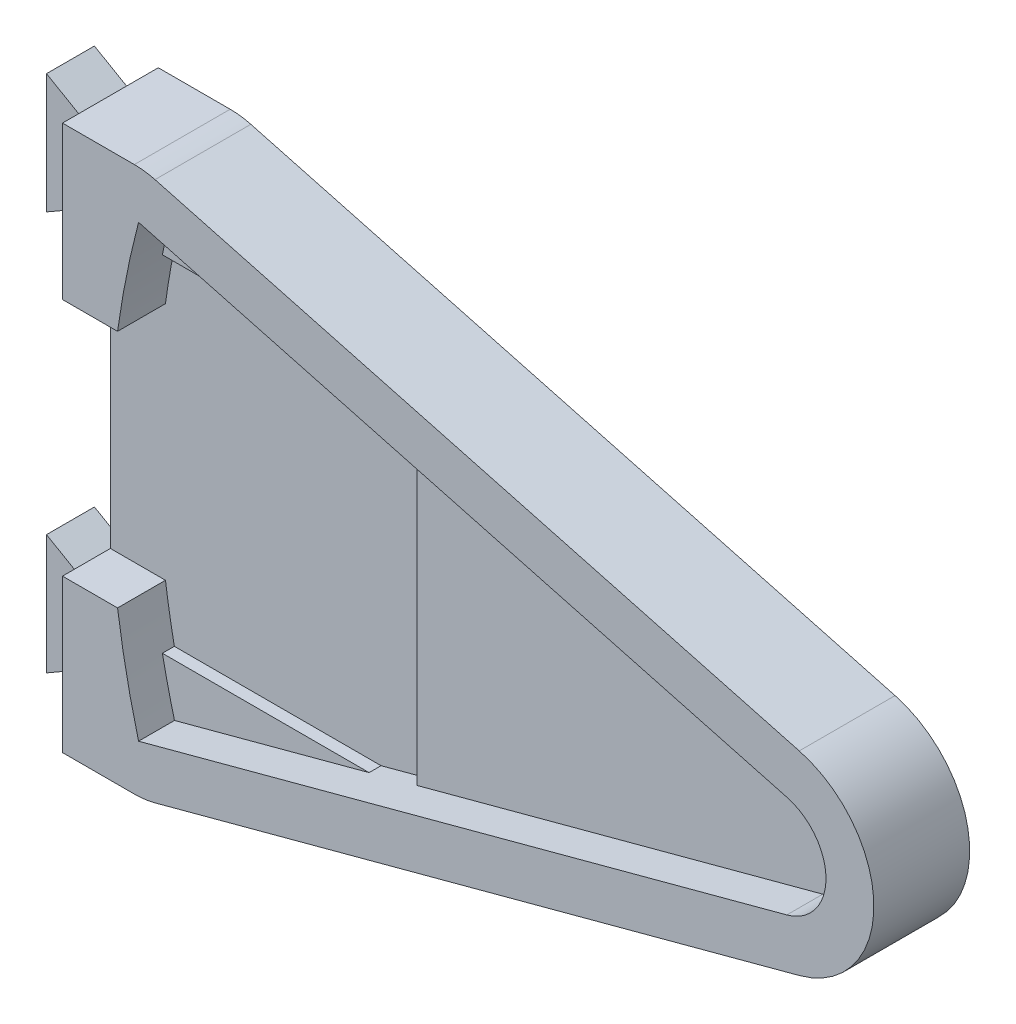
SolidWorks part; units mm, degrees
ref_plane "Front Plane" through (0, 0, 0) normal (0, 0, 1) x (1, 0, 0)
ref_plane "Top Plane" through (0, 0, 0) normal (0, 1, 0) x (1, 0, 0)
ref_plane "Right Plane" through (0, 0, 0) normal (1, 0, 0) x (0, 0, -1)
sketch "Sketch1" plane through (0, 0, 0) normal (0, 0, 1) x (1, 0, 0)
  line L0 (-4.8058, 6.263) -> (-85.8802, 27.9868) construction
  line L1 (-85.8802, -27.9868) -> (-4.8058, -6.263) construction
  line L2 (-89.5, 0) -> (0, 0) construction
  line L3 (-85.9704, -28.1425) -> (-4.7729, -6.3857)
  line L4 (-4.7729, 6.3857) -> (-85.9704, 28.1425)
  line L5 (-83.9089, -33.8018) -> (-3.22, -12.1813)
  line L6 (-3.22, 12.1813) -> (-83.9089, 33.8018)
  line L7 (-95.5, 34.1425) -> (-95.5, -34.1425)
  line L8 (-89.5, 0) -> (-95.5, 0) construction
  line L9 (-84.4175, -33.9381) -> (-3.22, -12.1813) construction
  line L10 (-3.22, 12.1813) -> (-84.4175, 33.9381) construction
  line L11 (-95.5, 34.1425) -> (-86.4971, 34.1425)
  line L12 (-95.5, -34.1425) -> (-86.4971, -34.1425)
  arc A0 (-85.8802, 27.9868) -> (-85.8802, -27.9868) centre (20.5, 0) ccw construction
  arc A1 (-4.8058, -6.263) -> (-4.8058, 6.263) centre (-6.484, 0) ccw construction
  arc A2 (-85.9704, 28.1425) -> (-85.9704, -28.1425) centre (20.5, 0) ccw
  arc A3 (-4.7729, -6.3857) -> (-4.7729, 6.3857) centre (-6.484, 0) ccw
  arc A4 (-3.22, -12.1813) -> (-3.22, 12.1813) centre (-6.484, 0) ccw
  arc A5 (-86.4971, 34.1425) -> (-83.9089, 33.8018) centre (-86.4971, 24.1425) cw
  arc A6 (-86.4971, -34.1425) -> (-83.9089, -33.8018) centre (-86.4971, -24.1425) ccw
  point P6 (0, 0)
  point P23 (-95.5, 0)
  dimension "D1" = 110
  dimension "D2" = 6.484
  dimension "D12" = 10
  dimension "D14" = 10
  dimension "D3" = 81.0744
  dimension "D4" = 81.0744
  dimension "D5" = 21.7238
  dimension "D6" = 21.7238
  dimension "D7" = 55.9737
  dimension "D10" = 6
  dimension "D11" = 6
  dimension "D13" = 6
  dimension "D8" = 0.127
  dimension "D9" = 6
extrude "Boss-Extrude1" add sketch "Sketch1" along normal blind 6 contours L3 A3 L4 A2 | L12 A6 L5 A4 L6 A5 L11 L7 A3 L3 A2 L4 region at (-54.6517, 0, 0) region at (-85.3516, -32.8431, 0)
extrude "Boss-Extrude2" add sketch "Sketch1<3>" along normal blind 6 from surface starting at face at (-66.1103, 0, 6)
sketch "Sketch1<3>" plane through (0, 0, 0) normal (0, 0, 1) x (1, 0, 0) same geometry as "Sketch1"
sketch "Sketch2" plane through (0, 0, 0) normal (0, 0, 1) x (1, 0, 0)
  line L4 (0, 0) -> (-95.5, 0) construction
  line L6 (-95.5, -34.1425) -> (-95.5, 34.1425) construction
  line L7 (-95.5, 27.8812) -> (-103.5, 32.5)
  line L8 (-103.5, 32.5) -> (-103.5, 17.5)
  line L9 (-103.5, 17.5) -> (-95.5, 22.1188)
  line L10 (-103.5, -17.5) -> (-95.5, -22.1188)
  line L11 (-103.5, -32.5) -> (-103.5, -17.5)
  line L12 (-95.5, -27.8812) -> (-103.5, -32.5)
  line L13 (-95.5, 27.8812) -> (-95.5, 22.1188)
  line L14 (-95.5, -22.1188) -> (-95.5, -27.8812)
  point P4 (-103.5, 25)
  dimension "D1" = 25
  dimension "D2" = 60
  dimension "D3" = 60
  dimension "D4" = 15
  dimension "D5" = 8
extrude "Boss-Extrude3" add sketch "Sketch2" along normal blind 6
sketch "Sketch3" plane through (-95.5, 0, 0) normal (-1, 0, 0) x (0, 0, 1)
  line L0 (12, -34.1425) -> (12, 34.1425) construction
  line L1 (12, 15) -> (6, 15)
  line L2 (12, 15) -> (12, -15)
  line L3 (12, -15) -> (6, -15)
  line L4 (6, 15) -> (6, -15)
  line L6 (0, 0) -> (50000, 0) construction
  line L8 (6, 32.5) -> (6, 17.5) construction
  point P13 (6, 0)
  dimension "D1" = 15
extrude "Cut-Extrude1" cut sketch "Sketch3" against normal blind 10
sketch "Sketch4" plane through (0, 0, 6) normal (0, 0, 1) x (1, 0, 0)
  line L0 (0.127, 0) -> (-49999.873, 0) construction
  line L1 (-85.5822, 20) -> (-55.5822, 20) construction
  line L2 (-85.5822, 20) -> (-85.5822, -20) construction
  line L3 (-85.5822, -20) -> (-55.5822, -20) construction
  line L4 (-55.5822, 20) -> (-55.5822, -20)
  line L5 (-4.7729, -6.3857) -> (-85.9704, -28.1425) construction
  line L6 (-85.9704, 28.1425) -> (-4.7729, 6.3857) construction
  line L7 (-4.7729, -6.3857) -> (-55.5822, -20)
  line L8 (-55.5822, 20) -> (-4.7729, 6.3857)
  line L9 (-87.4857, 21.6113) -> (-61.5957, 21.6113)
  line L10 (-85.9704, 28.1425) -> (-61.5957, 21.6113)
  line L11 (-85.9704, -28.1425) -> (-61.5957, -21.6113)
  line L12 (-87.4857, -21.6113) -> (-61.5957, -21.6113)
  arc A0 (-4.7729, -6.3857) -> (-4.7729, 6.3857) centre (-6.484, 0) ccw construction
  arc A1 (-4.7729, -6.3857) -> (-4.7729, 6.3857) centre (-6.484, 0) ccw
  arc A2 (-85.9704, 28.1425) -> (-88.6007, 15) centre (20.5, 0) ccw construction
  arc A3 (-85.9704, 28.1425) -> (-87.4857, 21.6113) centre (20.5, 0) ccw
  arc A4 (-85.9704, -28.1425) -> (-87.4857, -21.6113) centre (20.5, 0) cw
  point P9 (0.127, 0)
  point P10 (-55.5822, 0)
  dimension "D1" = 30
  dimension "D2" = 40
extrude "Boss-Extrude4" add sketch "Sketch4" along normal blind 1.5
